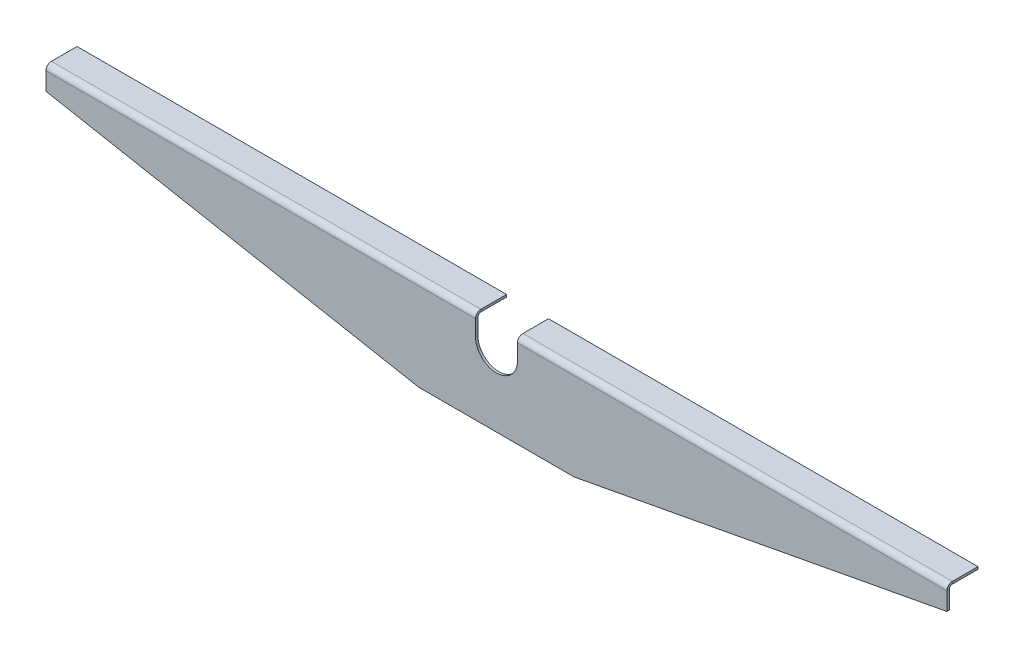
SolidWorks part; units mm, degrees
note: The reader was unsure of these and kept them because the rebuilt part matched: flange length of "Edge-Flange1".
material "Galvanized Steel"
ref_plane "Front Plane" through (0, 0, 0) normal (0, 0, 1) x (1, 0, 0)
ref_plane "Top Plane" through (0, 0, 0) normal (0, 1, 0) x (1, 0, 0)
ref_plane "Right Plane" through (0, 0, 0) normal (1, 0, 0) x (0, 0, -1)
sketch "Sketch1" plane through (0, 0, 0) normal (0, 0, 1) x (1, 0, 0)
  line L0 (-290, 10) -> (290, 10)
  line L1 (290, 10) -> (290, -5)
  line L2 (290, -5) -> (50, -50)
  line L3 (50, -50) -> (-50, -50)
  line L4 (-50, -50) -> (-290, -5)
  line L5 (-290, -5) -> (-290, 10)
  point P7 (0, 10)
  point P9 (0, -50)
  dimension "D1" = 580
  dimension "D2" = 15
  dimension "D3" = 60
  dimension "D4" = 15
  dimension "D5" = 50
  dimension "D6" = 100
base flange "Base-Flange2" sketch "Sketch1" thickness 1.5 reverse thickness direction no parameters "D1"=2
edge flange "Edge-Flange1" sketch "Sketch12" flange angle 90 flange length 20 flange position material inside bend radius 2 thickness 1.5 relief obround parameters "D6"=10
sketch "Sketch12" plane through (0, 10, -1.5) normal (0, 1, 0) x (1, 0, 0)
  line L0 (290, 0) -> (-290, 0) construction
  line L1 (290, 0) -> (-290, 0)
  line L2 (-290, 0) -> (-290, 18.5)
  line L3 (-290, 18.5) -> (290, 18.5)
  line L4 (290, 18.5) -> (290, 0)
bend "EdgeBend1" bend radius 2 bend angle 90 parameters "D5"=1
sketch "Sketch13" plane through (0, 0, 0) normal (0, 0, 1) x (1, 0, 0)
  line L0 (-13.5, -3.5) -> (-13.5, 21.0126)
  line L2 (13.5, -3.5) -> (13.5, 21.0126)
  line L3 (13.5, 21.0126) -> (-13.5, 21.0126)
  arc A0 (-13.5, -3.5) -> (13.5, -3.5) centre (0, -3.5) ccw
  dimension "D1" = 27
extrude "Cut-Extrude1" cut sketch "Sketch13" against normal through all contours L3 L0 A0 L2 normal cut yes
sketch "Bend-Lines3" [suppressed] plane through (0, 0, 0) normal (0, 1, 0) x (1, 0, 0)
sketch "Bounding-Box3" [suppressed] plane through (0, 0, 0) normal (0, 1, 0) x (1, 0, 0)
sheet metal parameters "Sheet-Metal2" thickness 1.5 parameters "D1"=2
flat pattern "Flat-Pattern2" [suppressed]
sketch "Bend-Lines4" plane through (0, 0, 0) normal (0, 1, 0) x (1, 0, 0)
sketch3d "Bounding-Box4" [suppressed]
  line L0 (165, -50, 0) -> (-165, -50, 0) construction
  line L1 (165, 10, 0) -> (-165, 10, 0) construction
  line L2 (165, -50, 0) -> (165, 10, 0) construction
  line L3 (-165, -50, 0) -> (-165, 10, 0) construction
sheet metal parameters "Sheet-Metal3" thickness 1.5 parameters "D1"=2
flat pattern "Flat-Pattern2"
sketch "Bend-Lines4" plane through (0, 0, 0) normal (0, 0, 1) x (1, 0, 0)
  line L0 (165, 8.6598) -> (-165, 8.6598) construction
  line L1 (165, 8.6598) -> (-165, 8.6598) construction
sketch3d "Bounding-Box4" [suppressed]
  line L0 (-165, -50, 0) -> (165, -50, 0) construction
  line L1 (-165, 27.3197, 0) -> (165, 27.3197, 0) construction
  line L2 (-165, -50, 0) -> (-165, 27.3197, 0) construction
  line L3 (165, -50, 0) -> (165, 27.3197, 0) construction
bend of the flat pattern "Flatten-<EdgeBend1>1"
sheet metal parameters "Sheet-Metal4" thickness 1.5 parameters "D1"=2
flat pattern "Flat-Pattern2"
sketch "Bend-Lines4" plane through (0, 0, 0) normal (0, 0, 1) x (1, 0, 0)
  line L0 (290, 8.6598) -> (13.5, 8.6598) construction
  line L1 (290, 8.6598) -> (13.5, 8.6598) construction
  line L2 (-13.5, 8.6598) -> (-290, 8.6598) construction
sketch3d "Bounding-Box4" [suppressed]
  line L0 (-290, -50, 0) -> (290, -50, 0) construction
  line L1 (-290, 27.3197, 0) -> (290, 27.3197, 0) construction
  line L2 (-290, -50, 0) -> (-290, 27.3197, 0) construction
  line L3 (290, -50, 0) -> (290, 27.3197, 0) construction
bend of the flat pattern "Flatten-<EdgeBend1>1"
